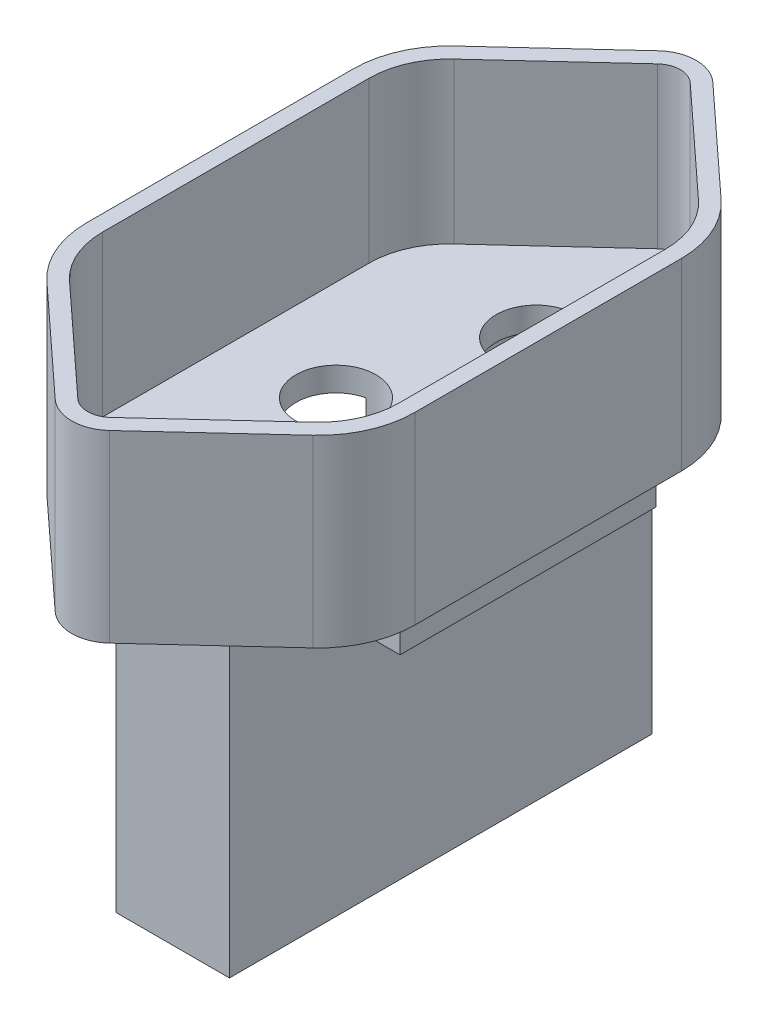
SolidWorks part; units mm, degrees
ref_plane "Plano frontal" through (0, 0, 0) normal (0, 0, 1) x (1, 0, 0)
ref_plane "Plano superior" through (0, 0, 0) normal (0, 1, 0) x (1, 0, 0)
ref_plane "Plano direito" through (0, 0, 0) normal (1, 0, 0) x (0, 0, -1)
sketch "Esboço1" plane through (0, 0, 0) normal (0, 1, 0) x (1, 0, 0)
  line L1 (-13.35, 19.65) -> (13.35, 19.65)
  line L2 (-13.35, 19.65) -> (-13.35, -19.65)
  line L3 (-13.35, -19.65) -> (13.35, -19.65)
  line L4 (13.35, 19.65) -> (13.35, -19.65)
  line L5 (-13.35, 19.65) -> (13.35, -19.65) construction
  line L6 (-13.35, -19.65) -> (13.35, 19.65) construction
  point P0 (0, 0)
  dimension "D1" = 26.7
  dimension "D2" = 39.3
extrude "Ressalto-extrusão1" add sketch "Esboço1" against normal blind 38.5
sketch "Esboço2" plane through (0, 0, 0) normal (0, 1, 0) x (1, 0, 0)
  line L0 (0, -19.04) -> (0, 19.04) construction
  line L1 (1.0166, -18.1029) -> (7.6387, -11.9991)
  line L2 (9.25, -8.3226) -> (9.25, 8.3226)
  line L3 (7.6387, 11.9991) -> (1.0166, 18.1029)
  line L4 (0, 0) -> (9.25, 0) construction
  line L5 (-1.0166, -18.1029) -> (-7.6387, -11.9991)
  line L6 (-7.6387, 11.9991) -> (-1.0166, 18.1029)
  line L7 (-9.25, -8.3226) -> (-9.25, 8.3226)
  arc A0 (9.25, 8.3226) -> (7.6387, 11.9991) centre (4.25, 8.3226) ccw
  arc A1 (7.6387, -11.9991) -> (9.25, -8.3226) centre (4.25, -8.3226) ccw
  arc A2 (-7.6387, -11.9991) -> (-9.25, -8.3226) centre (-4.25, -8.3226) cw
  arc A3 (-9.25, 8.3226) -> (-7.6387, 11.9991) centre (-4.25, 8.3226) cw
  arc A4 (1.0166, 18.1029) -> (-1.0166, 18.1029) centre (0, 17) ccw
  arc A5 (1.0166, -18.1029) -> (-1.0166, -18.1029) centre (0, -17) cw
  point P3 (0, 0)
  dimension "D1" = 5
  dimension "D2" = 1.5
  dimension "D3" = 37
  dimension "D4" = 28
  dimension "D5" = 18.5
extrude "Corte-extrusão1" cut sketch "Esboço2" against normal blind 10 contours A5 L1 A1 L2 A0 L3 A4 L6 A3 L7 A2 L5
sketch "Esboço4" plane through (0, 0, 0) normal (0, 1, 0) x (1, 0, 0)
  line L14 (-8.3165, -12.7344) -> (-1.6944, -18.8382)
  line L15 (1.6944, -18.8382) -> (8.3165, -12.7344)
  line L16 (10.25, -8.3226) -> (10.25, 8.3226)
  line L17 (8.3165, 12.7344) -> (1.6944, 18.8382)
  line L18 (-1.6944, 18.8382) -> (-8.3165, 12.7344)
  line L19 (-10.25, 8.3226) -> (-10.25, -8.3226)
  line L20 (1.0166, -18.1029) -> (7.6387, -11.9991)
  line L21 (9.25, -8.3226) -> (9.25, 8.3226)
  line L22 (7.6387, 11.9991) -> (1.0166, 18.1029)
  line L23 (-1.0166, 18.1029) -> (-7.6387, 11.9991)
  line L24 (-9.25, 8.3226) -> (-9.25, -8.3226)
  line L25 (-7.6387, -11.9991) -> (-1.0166, -18.1029)
  line L26 (1.0166, -18.1029) -> (7.6387, -11.9991)
  line L27 (9.25, -8.3226) -> (9.25, 8.3226)
  line L28 (7.6387, 11.9991) -> (1.0166, 18.1029)
  line L29 (-1.0166, 18.1029) -> (-7.6387, 11.9991)
  line L30 (-9.25, 8.3226) -> (-9.25, -8.3226)
  line L31 (-7.6387, -11.9991) -> (-1.0166, -18.1029)
  line L36 (13.35, -19.65) -> (13.35, 19.65)
  line L37 (13.35, 19.65) -> (-13.35, 19.65)
  line L38 (-13.35, 19.65) -> (-13.35, -19.65)
  line L39 (-13.35, -19.65) -> (13.35, -19.65)
  line L40 (13.35, -19.65) -> (13.35, 19.65)
  line L41 (13.35, 19.65) -> (-13.35, 19.65)
  line L42 (-13.35, 19.65) -> (-13.35, -19.65)
  line L43 (-13.35, -19.65) -> (13.35, -19.65)
  arc A6 (-10.25, -8.3226) -> (-8.3165, -12.7344) centre (-4.25, -8.3226) ccw
  arc A7 (-1.6944, -18.8382) -> (1.6944, -18.8382) centre (0, -17) ccw
  arc A8 (8.3165, -12.7344) -> (10.25, -8.3226) centre (4.25, -8.3226) ccw
  arc A9 (10.25, 8.3226) -> (8.3165, 12.7344) centre (4.25, 8.3226) ccw
  arc A10 (1.6944, 18.8382) -> (-1.6944, 18.8382) centre (0, 17) ccw
  arc A11 (-8.3165, 12.7344) -> (-10.25, 8.3226) centre (-4.25, 8.3226) ccw
  arc A12 (7.6387, -11.9991) -> (9.25, -8.3226) centre (4.25, -8.3226) ccw
  arc A13 (9.25, 8.3226) -> (7.6387, 11.9991) centre (4.25, 8.3226) ccw
  arc A14 (1.0166, 18.1029) -> (-1.0166, 18.1029) centre (0, 17) ccw
  arc A15 (-7.6387, 11.9991) -> (-9.25, 8.3226) centre (-4.25, 8.3226) ccw
  arc A16 (-9.25, -8.3226) -> (-7.6387, -11.9991) centre (-4.25, -8.3226) ccw
  arc A17 (-1.0166, -18.1029) -> (1.0166, -18.1029) centre (0, -17) ccw
  arc A18 (7.6387, -11.9991) -> (9.25, -8.3226) centre (4.25, -8.3226) ccw
  arc A19 (9.25, 8.3226) -> (7.6387, 11.9991) centre (4.25, 8.3226) ccw
  arc A20 (1.0166, 18.1029) -> (-1.0166, 18.1029) centre (0, 17) ccw
  arc A21 (-7.6387, 11.9991) -> (-9.25, 8.3226) centre (-4.25, 8.3226) ccw
  arc A22 (-9.25, -8.3226) -> (-7.6387, -11.9991) centre (-4.25, -8.3226) ccw
  arc A23 (-1.0166, -18.1029) -> (1.0166, -18.1029) centre (0, -17) ccw
  line M41 (13.35, -19.65) -> (13.35, 19.65)
  line M42 (13.35, 19.65) -> (-13.35, 19.65)
  line M43 (-13.35, 19.65) -> (-13.35, -19.65)
  line M44 (-13.35, -19.65) -> (13.35, -19.65)
  dimension "D1" = 0
  dimension "D2" = 1
  dimension "D3" = 0
extrude "Corte-extrusão2" cut sketch "Esboço4" against normal blind 10 contours A11 L18 A10 L17 A9 L16 A8 L15 A7 L14 A6 L19 M44 M41 M42 M43 region at (0, 0, 19.6025)
sketch "Esboço5" plane through (0, -38.5, 0) normal (0, -1, 0) x (1, 0, 0)
  line L1 (11.3, -13.5) -> (-11.3, -13.5)
  line L2 (11.3, -13.5) -> (11.3, 13.5)
  line L3 (11.3, 13.5) -> (-11.3, 13.5)
  line L4 (-11.3, -13.5) -> (-11.3, 13.5)
  line L5 (11.3, -13.5) -> (-11.3, 13.5) construction
  line L6 (11.3, 13.5) -> (-11.3, -13.5) construction
  line L10 (13.35, -19.65) -> (13.35, 19.65)
  line L11 (13.35, 19.65) -> (-13.35, 19.65)
  line L12 (-13.35, 19.65) -> (-13.35, -19.65)
  line L13 (-13.35, -19.65) -> (13.35, -19.65)
  line L14 (13.35, -19.65) -> (13.35, 19.65)
  line L15 (13.35, 19.65) -> (-13.35, 19.65)
  line L16 (-13.35, 19.65) -> (-13.35, -19.65)
  line L17 (-13.35, -19.65) -> (13.35, -19.65)
  point P0 (0, 0)
  line M3 (13.35, -19.65) -> (13.35, 19.65)
  line M4 (13.35, 19.65) -> (-13.35, 19.65)
  line M5 (-13.35, 19.65) -> (-13.35, -19.65)
  line M6 (-13.35, -19.65) -> (13.35, -19.65)
  dimension "D1" = 27
  dimension "D2" = 22.6
  dimension "D3" = 0
extrude "Corte-extrusão4" cut sketch "Esboço5" against normal blind 27 contours L1 L4 L3 L2 M6 M3 M4 M5 region at (0, -38.5, -19.1749)
sketch "Esboço6" plane through (0, -10, 0) normal (0, 1, 0) x (1, 0, 0)
  line L0 (0, -9.5) -> (0, 9.5) construction
  line L1 (0, 0) -> (-3, 0) construction
  circle A0 centre (0, -9.5) radius 2.5
  circle A1 centre (0, 9.5) radius 2.5
  circle A2 centre (-3, 0) radius 2.5
  point P3 (0, 0)
  dimension "D1" = 5
  dimension "D2" = 19
  dimension "D3" = 3
extrude "Corte-extrusão5" cut sketch "Esboço6" against normal blind 5
sketch "Esboço7" plane through (0, -11.5, 0) normal (0, -1, 0) x (1, 0, 0)
  line L0 (13.35, -19.65) -> (13.35, 19.65) construction
  line L1 (11.3, 13.5) -> (13.35, 13.5)
  line L2 (11.3, 13.5) -> (11.3, 12.5)
  line L3 (11.3, 12.5) -> (13.35, 12.5)
  line L4 (13.35, 13.5) -> (13.35, 12.5)
  line L5 (0, 0) -> (0, 13.5) construction
  line L6 (11.3, 13.5) -> (-11.3, 13.5) construction
  line L7 (0, 0) -> (11.3, 0) construction
  line L8 (11.3, -13.5) -> (11.3, 13.5) construction
  line L9 (-13.35, 13.5) -> (-13.35, 12.5)
  line L10 (-11.3, 12.5) -> (-13.35, 12.5)
  line L11 (-11.3, 13.5) -> (-11.3, 12.5)
  line L12 (-11.3, 13.5) -> (-13.35, 13.5)
  line L13 (-11.3, -13.5) -> (-13.35, -13.5)
  line L14 (-11.3, -13.5) -> (-11.3, -12.5)
  line L15 (-11.3, -12.5) -> (-13.35, -12.5)
  line L16 (-13.35, -13.5) -> (-13.35, -12.5)
  line L17 (13.35, -13.5) -> (13.35, -12.5)
  line L18 (11.3, -12.5) -> (13.35, -12.5)
  line L19 (11.3, -13.5) -> (11.3, -12.5)
  line L20 (11.3, -13.5) -> (13.35, -13.5)
  dimension "D1" = 1
extrude "Ressalto-extrusão2" add sketch "Esboço7" along normal blind 4
sketch "Sketch2" plane through (11.3, 0, 0) normal (1, 0, 0) x (0, 0, -1)
  line L6 (-13.5, -11.5) -> (13.5, -11.5)
  line L7 (-13.5, -11.5) -> (-13.5, -38.5)
  line L8 (-13.5, -38.5) -> (13.5, -38.5)
  line L9 (13.5, -11.5) -> (13.5, -38.5)
extrude "Cut-Extrude1" cut sketch "Sketch2" against normal blind 100 and the other way blind 10
extrude "Cut-Extrude3" cut sketch "Esboço4<3>" against normal blind 100 contours A11 L18 A10 L17 A9 L16 A8 L15 A7 L14 A6 L19 M44 M41 M42 M43 region at (0, 0, 19.6025)
sketch "Esboço4<3>" plane through (0, 0, 0) normal (0, 1, 0) x (1, 0, 0) same geometry as "Esboço4"
sketch "Sketch6" plane through (0, -11.5, 0) normal (0, -1, 0) x (1, 0, 0)
  line L0 (-3.55, 2.4387) -> (-3.55, 13.2)
  line L1 (3.55, -8) -> (3.55, 8)
  line L2 (3.55, -8) -> (9, -8)
  line L3 (9, -8) -> (9, 8)
  line L4 (3.55, 8) -> (9, 8)
  line L5 (-3.55, -13.2) -> (-3.55, -2.4387)
  line L6 (-3.55, -13.2) -> (3.55, -13.2)
  line L7 (3.55, -13.2) -> (3.55, 13.2)
  line L8 (-3.55, 13.2) -> (3.55, 13.2)
  line L9 (-2.75, -12.4) -> (-2.75, -3.2905)
  line L10 (-2.75, -12.4) -> (2.75, -12.4)
  line L11 (2.75, -12.4) -> (2.75, -0.4)
  line L12 (0.2757, -0.4) -> (2.75, -0.4)
  line L13 (2.75, 0.4) -> (2.75, 12.4)
  line L14 (2.75, 0.4) -> (0.2757, 0.4)
  line L15 (-2.75, 3.2905) -> (-2.75, 12.4)
  line L16 (2.75, 12.4) -> (-2.75, 12.4)
  circle A0 centre (7, -5.75) radius 1
  circle A1 centre (7, 5.75) radius 1
  arc A2 (-3.55, -2.4387) -> (-3.55, 2.4387) centre (-3, 0) ccw
  arc A3 (-2.75, -3.2905) -> (0.2757, -0.4) centre (-3, 0) ccw
  arc A4 (0.2757, 0.4) -> (-2.75, 3.2905) centre (-3, 0) ccw
  circle M21 centre (-3, 0) radius 2.5
extrude "Boss-Extrude1" add sketch "Sketch6" along normal blind 20 contours L8 L0 L5 L6 L7 L1 L9 A3 L12 L11 L10 L14 A4 L15 L16 L13 M21 region at (0.1491, -11.5, 0)
extrude "Boss-Extrude2" add sketch "Sketch6<3>" along normal blind 2.4 contours L4 L1 L2 L3 A1 A0 region at (6.2187, -11.5, 0)
sketch "Sketch6<3>" plane through (0, -11.5, 0) normal (0, -1, 0) x (1, 0, 0) same geometry as "Sketch6"
